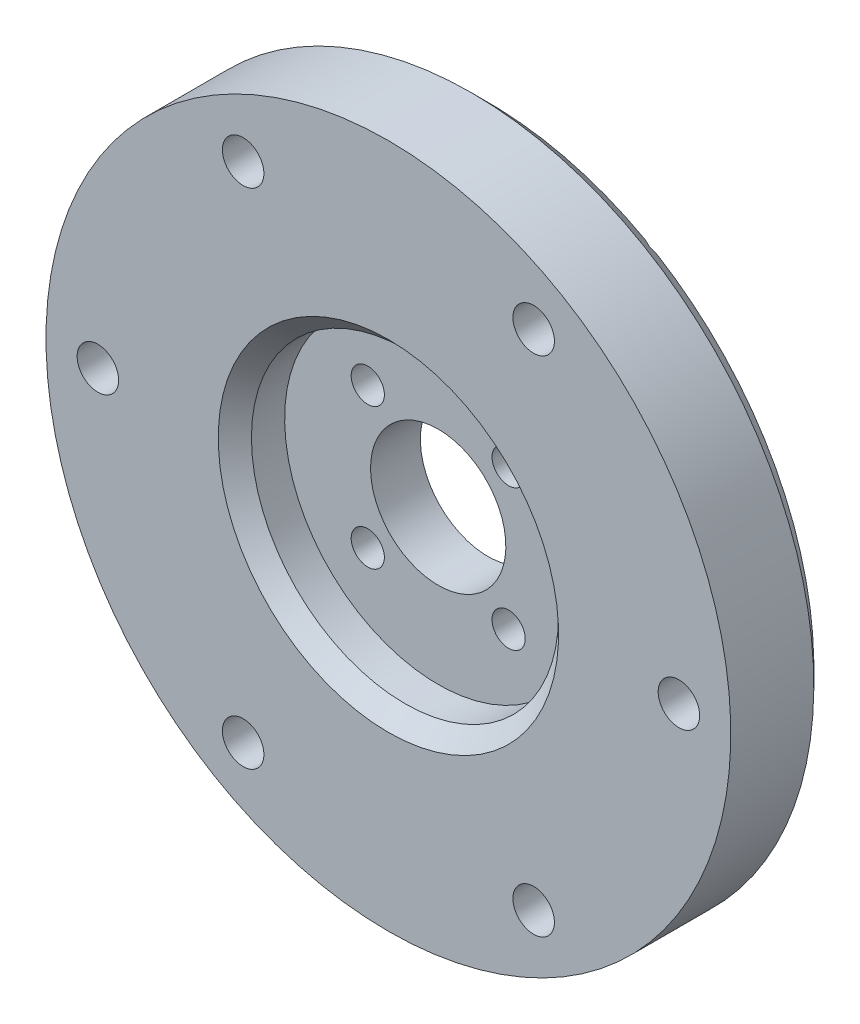
SolidWorks part; units mm, degrees
ref_plane "前视基准面" through (0, 0, 0) normal (0, 0, 1) x (1, 0, 0)
ref_plane "上视基准面" through (0, 0, 0) normal (0, 1, 0) x (1, 0, 0)
ref_plane "右视基准面" through (0, 0, 0) normal (1, 0, 0) x (0, 0, -1)
sketch "草图1" plane through (0, 0, 0) normal (1, 0, 0) x (0, 0, -1)
  line L0 (0, 41.25) -> (0, 18.5)
  line L1 (0, 41.25) -> (12, 41.25)
  line L5 (14, 0) -> (7, 0) construction
  line L6 (0, 18.5) -> (6, 18.5)
  line L8 (6, 8.15) -> (12, 8.15)
  line L9 (6, 18.5) -> (6, 8.15)
  line L10 (12, 8.15) -> (12, 41.25)
  point P2 (14, 40.9031)
  point P8 (0, 0)
  dimension "D1" = 41.25
  dimension "D4" = 6
  dimension "D5" = 18.5
  dimension "D6" = 6
  dimension "D7" = 8.15
revolve "旋转1" add sketch "草图1" angle 360 about L5
sketch "草图2" plane through (0, 0, 0) normal (0, 0, 1) x (1, 0, 0)
  line L1 (-8.4853, -8.4853) -> (8.4853, -8.4853) construction
  line L2 (-8.4853, -8.4853) -> (-8.4853, 8.4853) construction
  line L3 (-8.4853, 8.4853) -> (8.4853, 8.4853) construction
  line L4 (8.4853, -8.4853) -> (8.4853, 8.4853) construction
  line L5 (-8.4853, -8.4853) -> (8.4853, 8.4853) construction
  line L6 (-8.4853, 8.4853) -> (8.4853, -8.4853) construction
  line L7 (17.5, 30.3109) -> (-17.5, 30.3109) construction
  line L8 (-17.5, 30.3109) -> (-35, 0) construction
  line L9 (-35, 0) -> (-17.5, -30.3109) construction
  line L10 (-17.5, -30.3109) -> (17.5, -30.3109) construction
  line L11 (17.5, -30.3109) -> (35, 0) construction
  line L12 (35, 0) -> (17.5, 30.3109) construction
  circle A0 centre (0, 0) radius 30.3109 construction
  circle A1 centre (-17.5, 30.3109) radius 2.5
  circle A2 centre (17.5, 30.3109) radius 2.5
  circle A3 centre (35, 0) radius 2.5
  circle A4 centre (17.5, -30.3109) radius 2.5
  circle A5 centre (-17.5, -30.3109) radius 2.5
  circle A6 centre (-35, 0) radius 2.5
  circle A7 centre (-8.4853, 8.4853) radius 2
  circle A8 centre (8.4853, 8.4853) radius 2
  circle A9 centre (8.4853, -8.4853) radius 2
  circle A10 centre (-8.4853, -8.4853) radius 2
  point P0 (0, 0)
  dimension "D2" = 5
  dimension "D4" = 4
  dimension "D1" = 70
  dimension "D3" = 24
extrude "切除-拉伸1" cut sketch "草图2" against normal through all
sketch "草图3" plane through (0, 0, -12) normal (0, 0, -1) x (-1, 0, 0)
  line L1 (-12.8235, 30.3109) -> (-15.1617, 34.3609)
  line L2 (-15.1617, 34.3609) -> (-19.8383, 34.3609)
  line L3 (-19.8383, 34.3609) -> (-22.1765, 30.3109)
  line L4 (-22.1765, 30.3109) -> (-19.8383, 26.2609)
  line L5 (-19.8383, 26.2609) -> (-15.1617, 26.2609)
  line L6 (-15.1617, 26.2609) -> (-12.8235, 30.3109)
  line L7 (19.8383, 26.2609) -> (22.1765, 30.3109)
  line L8 (22.1765, 30.3109) -> (19.8383, 34.3609)
  line L9 (19.8383, 34.3609) -> (15.1617, 34.3609)
  line L10 (15.1617, 34.3609) -> (12.8235, 30.3109)
  line L11 (12.8235, 30.3109) -> (15.1617, 26.2609)
  line L12 (15.1617, 26.2609) -> (19.8383, 26.2609)
  line L13 (32.6617, -4.05) -> (37.3383, -4.05)
  line L14 (37.3383, -4.05) -> (39.6765, 0)
  line L15 (39.6765, 0) -> (37.3383, 4.05)
  line L16 (37.3383, 4.05) -> (32.6617, 4.05)
  line L17 (32.6617, 4.05) -> (30.3235, 0)
  line L18 (30.3235, 0) -> (32.6617, -4.05)
  line L19 (19.8383, -26.2609) -> (15.1617, -26.2609)
  line L20 (15.1617, -26.2609) -> (12.8235, -30.3109)
  line L21 (12.8235, -30.3109) -> (15.1617, -34.3609)
  line L22 (15.1617, -34.3609) -> (19.8383, -34.3609)
  line L23 (19.8383, -34.3609) -> (22.1765, -30.3109)
  line L24 (22.1765, -30.3109) -> (19.8383, -26.2609)
  line L25 (-15.1617, -26.2609) -> (-19.8383, -26.2609)
  line L26 (-19.8383, -26.2609) -> (-22.1765, -30.3109)
  line L27 (-22.1765, -30.3109) -> (-19.8383, -34.3609)
  line L28 (-19.8383, -34.3609) -> (-15.1617, -34.3609)
  line L29 (-15.1617, -34.3609) -> (-12.8235, -30.3109)
  line L30 (-12.8235, -30.3109) -> (-15.1617, -26.2609)
  line L31 (-32.6617, 4.05) -> (-37.3383, 4.05)
  line L32 (-37.3383, 4.05) -> (-39.6765, 0)
  line L33 (-39.6765, 0) -> (-37.3383, -4.05)
  line L34 (-37.3383, -4.05) -> (-32.6617, -4.05)
  line L35 (-32.6617, -4.05) -> (-30.3235, 0)
  line L36 (-30.3235, 0) -> (-32.6617, 4.05)
  circle A0 centre (-17.5, 30.3109) radius 4.05 construction
  circle A1 centre (17.5, 30.3109) radius 4.05 construction
  circle A2 centre (35, 0) radius 4.05 construction
  circle A3 centre (17.5, -30.3109) radius 4.05 construction
  circle A4 centre (-17.5, -30.3109) radius 4.05 construction
  circle A5 centre (-35, 0) radius 4.05 construction
  dimension "D1" = 8.1
extrude "切除-拉伸2" cut sketch "草图3" against normal offset from surface (6 mm away) 6 up to face at (-32.5, 0, 0)
chamfer "倒角1" distance 2 angle 45 2 edges at (0, 18.5, 0) (0, 41.25, -12)
